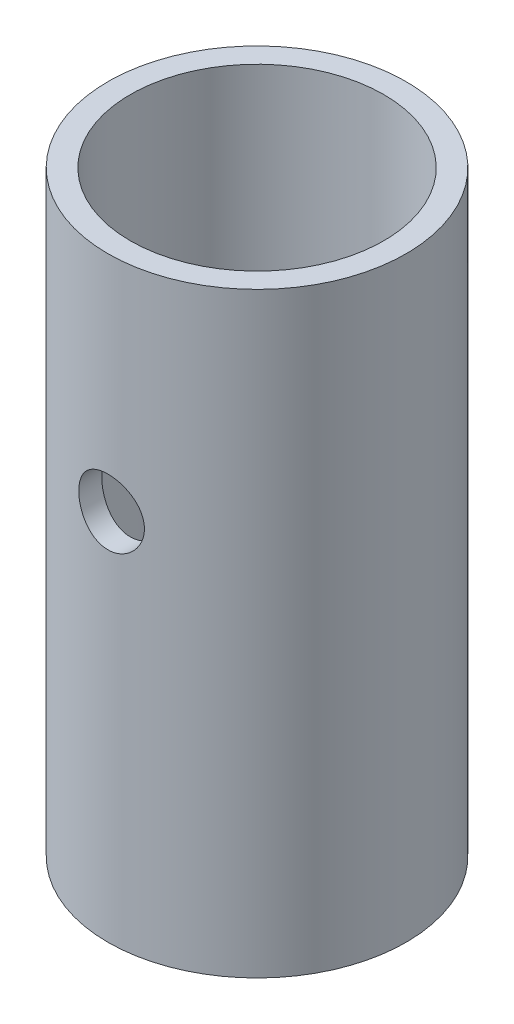
SolidWorks part; units mm, degrees
ref_plane "Front Plane" through (0, 0, 0) normal (0, 0, 1) x (1, 0, 0)
ref_plane "Top Plane" through (0, 0, 0) normal (0, 1, 0) x (1, 0, 0)
ref_plane "Right Plane" through (0, 0, 0) normal (1, 0, 0) x (0, 0, -1)
sketch "Sketch1" plane through (0, 0, 0) normal (0, 1, 0) x (1, 0, 0)
  circle A0 centre (0, 0) radius 5
  dimension "D1" = 10
extrude "Boss-Extrude1" add sketch "Sketch1" along normal blind 20 contours A0
sketch "Sketch2" plane through (0, 20, 0) normal (0, 1, 0) x (1, 0, 0)
  circle A0 centre (0, 0) radius 4.25
  dimension "D1" = 8.5
extrude "Cut-Extrude1" cut sketch "Sketch2" against normal blind 17.5 contours A0
sketch "Sketch3" plane through (0, 0, 0) normal (0, -1, 0) x (1, 0, 0)
  circle A0 centre (0, 0) radius 1.25
  dimension "D1" = 2.5
extrude "Cut-Extrude2" cut sketch "Sketch3" against normal blind 2.5
sketch "Sketch4" plane through (0, 0, 0) normal (0, 0, 1) x (1, 0, 0)
  line L0 (4.25, 20) -> (-4.25, 20) construction
  circle A0 centre (0, 12.5) radius 1.1
  dimension "D2" = 2.2
  dimension "D1" = 7.5
extrude "Cut-Extrude3" cut sketch "Sketch4" against normal blind 10 and the other way blind 10
